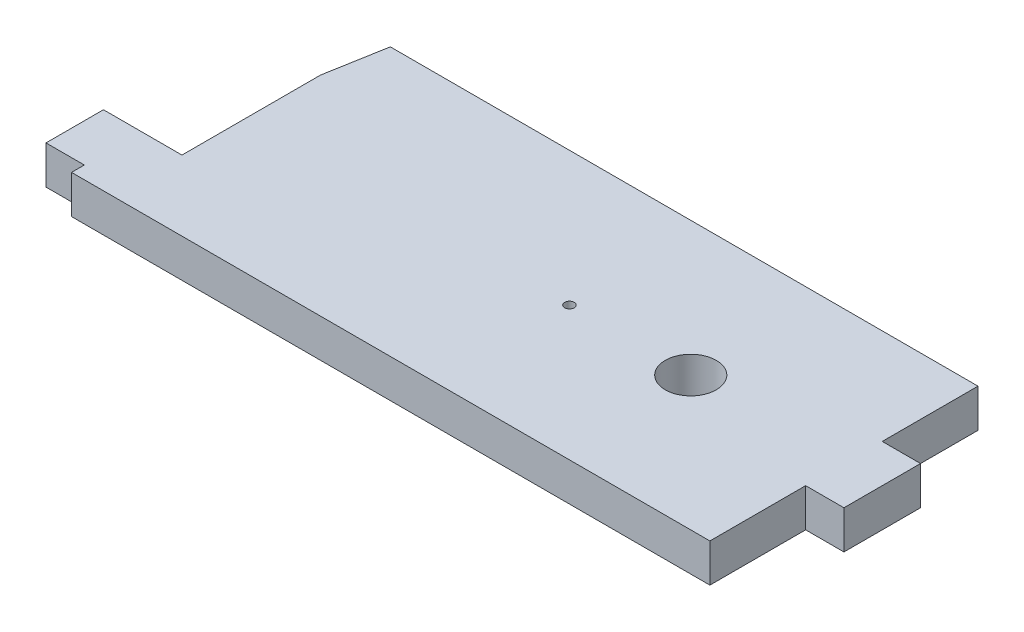
SolidWorks part; units mm, degrees
ref_plane "Front Plane" through (0, 0, 0) normal (0, 0, 1) x (1, 0, 0)
ref_plane "Top Plane" through (0, 0, 0) normal (0, 1, 0) x (1, 0, 0)
ref_plane "Right Plane" through (0, 0, 0) normal (1, 0, 0) x (0, 0, -1)
sketch "Sketch1" plane through (0, 0, 0) normal (0, 1, 0) x (1, 0, 0)
  line L1 (-47, 21) -> (47, 21)
  line L2 (-47, 21) -> (-47, -21)
  line L3 (-47, -21) -> (47, -21)
  line L4 (47, 21) -> (47, -21)
  line L5 (-47, 21) -> (47, -21) construction
  line L6 (-47, -21) -> (47, 21) construction
  point P0 (0, 0)
  dimension "D1" = 94
  dimension "D2" = 42
sketch "Sketch2" plane through (0, 0, 0) normal (0, 0, 1) x (1, 0, 0)
  line L0 (0, 0) -> (0, 6) construction
  line L1 (-47, 0) -> (47, 0) construction
  dimension "D1" = 6
extrude "Boss-Extrude1" add sketch "Sketch1" along normal up to vertex (6 mm away) contours L2 L3 L4 L1 up to point (0, 6, 0)
sketch "Sketch3" plane through (0, 0, 0) normal (0, -1, 0) x (1, 0, 0)
  line L0 (23, 0) -> (47, 0)
  line L1 (47, -21) -> (47, 21) construction
  circle A0 centre (23, 0) radius 4
  dimension "D1" = 8
  dimension "D2" = 24
extrude "Cut-Extrude1" cut sketch "Sketch3" against normal through all contours A0 region at (19.1131, 0, 0)
sketch "Sketch4" plane through (0, 6, 0) normal (0, 1, 0) x (1, 0, 0)
  line L0 (47, 21) -> (47, -21) construction
  line L1 (47, 6) -> (53, 6)
  line L2 (47, 6) -> (47, -6)
  line L3 (47, -6) -> (53, -6)
  line L4 (53, 6) -> (53, -6)
  line L5 (0, 0) -> (53, 0) construction
  dimension "D1" = 6
  dimension "D2" = 12
extrude "Boss-Extrude2" add sketch "Sketch4" against normal up to surface (6 mm away) up to face at (23, 0, -4)
sketch "Sketch5" plane through (0, 6, 0) normal (0, 1, 0) x (1, 0, 0)
  line L0 (0, 0) -> (-47, 0)
  line L1 (-47, 21) -> (-47, -21) construction
  line L2 (-47, 0) -> (-47, -10)
  line L3 (-47, -10) -> (-59, -10)
  line L4 (-59, -10) -> (-59, -19)
  line L5 (-59, -19) -> (-53, -19)
  line L6 (-53, -19) -> (-53, -21)
  line L7 (-53, -21) -> (-47, -21)
  line L8 (-47, -21) -> (-47, -10)
  line M9 (-47, 21) -> (-47, -21)
extrude "Boss-Extrude3" add sketch "Sketch5" against normal up to surface (6 mm away) contours L6 L7 L3 L4 L5 M9 region at (-52.7, 6, 15.05) up to face at (23, 0, -4)
sketch "Sketch6" plane through (0, 6, 0) normal (0, 1, 0) x (1, 0, 0)
  line L0 (23, -5) -> (23, 5) construction
  line L1 (19, -5) -> (19, 5)
  line L2 (27, -5) -> (27, 5)
  circle A0 centre (23, 0) radius 4 construction
  circle A1 centre (23, 0) radius 4
  arc A2 (19, -5) -> (27, -5) centre (23, -5) ccw
  arc A3 (27, 5) -> (19, 5) centre (23, 5) ccw
  point P5 (23, 0)
  dimension "D1" = 10
sketch "Sketch7" plane through (0, 0, 0) normal (0, -1, 0) x (1, 0, 0)
  line L12 (-47, -21) -> (47, -21)
  line L13 (47, -21) -> (47, -6)
  line L14 (47, -6) -> (53, -6)
  line L15 (53, -6) -> (53, 6)
  line L16 (53, 6) -> (47, 6)
  line L17 (47, 6) -> (47, 21)
  line L18 (47, 21) -> (-53, 21)
  line L19 (-53, 21) -> (-53, 19)
  line L20 (-53, 19) -> (-59, 19)
  line L21 (-59, 19) -> (-59, 10)
  line L22 (-59, 10) -> (-47, 10)
  line L23 (-47, 10) -> (-47, -21)
  line L24 (-47, -21) -> (47, -21)
  line L25 (47, -21) -> (47, -6)
  line L26 (47, -6) -> (53, -6)
  line L27 (53, -6) -> (53, 6)
  line L28 (53, 6) -> (47, 6)
  line L29 (47, 6) -> (47, 21)
  line L30 (47, 21) -> (-53, 21)
  line L31 (-53, 21) -> (-53, 19)
  line L32 (-53, 19) -> (-59, 19)
  line L33 (-59, 19) -> (-59, 10)
  line L34 (-59, 10) -> (-47, 10)
  line L35 (-47, 10) -> (-47, -21)
  circle A0 centre (4, 0) radius 0.75
  dimension "D2" = 1.5
  dimension "D1" = 0
extrude "Cut-Extrude2" cut sketch "Sketch7" against normal through all contours A0 region at (4, 0, 0)
sketch "Sketch8" plane through (0, 6, 0) normal (0, 1, 0) x (1, 0, 0)
  line L0 (-47, 10) -> (-45.0604, 21)
  line L1 (-47, 21) -> (-47, -10) construction
  line L2 (-47, 21) -> (47, 21) construction
  line L3 (-45.0604, 21) -> (-47, 21)
  line L4 (-47, 21) -> (-47, 10)
  line L5 (-53, 10) -> (-47, 10) construction
  line L6 (-47, -10) -> (-46.7, -10)
  line L7 (-46.7, -10) -> (-46.7, 11.7014)
  line L8 (-47, -10) -> (-47, 10)
  line M6 (47, 21) -> (-47, 21)
  line M7 (-47, 21) -> (-47, -10)
  dimension "D1" = 0.3
  dimension "D2" = 10
extrude "Cut-Extrude3" cut sketch "Sketch8" against normal through all contours L0 M7 M6 | L6 L7 L0 M7 region at (-46.3535, 6, -17.3333) region at (-46.848, 6, -0.4311)
equation "\"glass_width\"= 150"
equation "\"glass_height\"= 100"
equation "\"glass_thickness\"= 4"
equation "\"brood_space\"= 42"
equation "\"t1\"= 6"
equation "\"t2\"= 6"
equation "\"box_depth\"= \"brood_space\" + \"glass_thickness\" + \"glass_thickness\" + \"t2\" + \"t2\""
equation "\"box_width\"= \"glass_width\" + \"t1\" + \"t1\""
equation "\"food_height\"= 70"
equation "\"box_height\"= \"glass_height\" + ( \"t1\" * 3 ) + \"food_height\""
equation "\"D1@Sketch1\"=\"glass_height\" - \"t1\""
equation "\"D2@Sketch1\"=\"brood_space\""
equation "\"entry_height\"= 24"
equation "\"entry_diameter\"= 8"
equation "\"food_top_clearance\"= 10"
equation "\"bar_width\"= 20"
equation "\"glassblocker_lower_height\"= 10"
equation "\"D1@Sketch3\"=\"entry_diameter\""
equation "\"D2@Sketch3\"=\"entry_height\""
equation "\"D1@Sketch2\"=\"t2\""
equation "\"D1@Sketch4\"=\"t1\""
